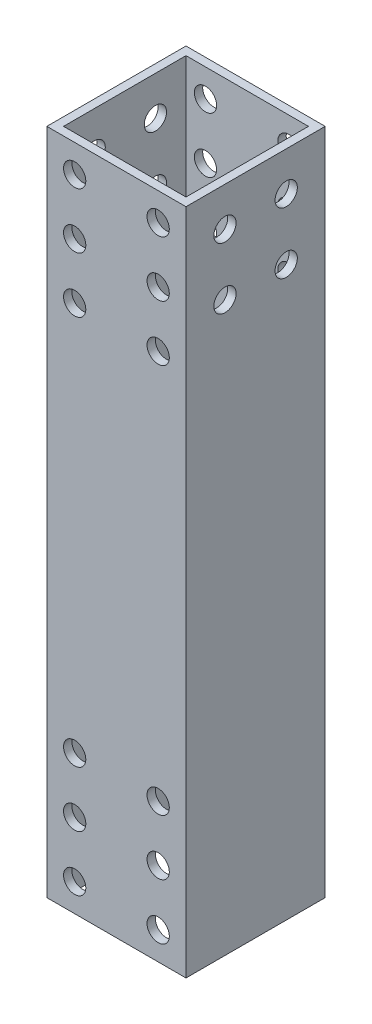
SolidWorks part; units mm, degrees
material "1060 Alloy"
ref_plane "Front Plane" through (0, 0, 0) normal (0, 0, 1) x (1, 0, 0)
ref_plane "Top Plane" through (0, 0, 0) normal (0, 1, 0) x (1, 0, 0)
ref_plane "Right Plane" through (0, 0, 0) normal (1, 0, 0) x (0, 0, -1)
sketch "Sketch1" plane through (0, 0, 0) normal (0, 1, 0) x (1, 0, 0)
  line L0 (0, 63.6278) -> (0, -69.3975) construction
  line L1 (-105.4586, 0) -> (105.4586, 0) construction
  line L2 (-11, 11) -> (-11, -11)
  line L3 (-12.5, 12.5) -> (12.5, 12.5)
  line L4 (-12.5, 12.5) -> (-12.5, -12.5)
  line L5 (-12.5, -12.5) -> (12.5, -12.5)
  line L6 (12.5, 12.5) -> (12.5, -12.5)
  line L7 (-11, -11) -> (11, -11)
  line L8 (11, 11) -> (11, -11)
  line L13 (-11, 11) -> (11, 11)
  point P5 (0, 0)
  dimension "D1" = 25
  dimension "D2" = 25
  dimension "D3" = 0
  dimension "D4" = 1.5
  dimension "D5" = 11
  dimension "D6" = 11
extrude "Boss-Extrude1" add sketch "Sketch1" along normal blind 60 and the other way blind 60
sketch "Sketch2" plane through (0, 0, -12.5) normal (0, 0, -1) x (-1, 0, 0)
  line L0 (0, 86.3155) -> (0, -83.2573) construction
  line L1 (-12.5, 60) -> (12.5, 60) construction
  circle A0 centre (7.5, 55) radius 2
  circle A1 centre (7.5, 45) radius 2
  circle A3 centre (-7.5, 55) radius 2
  circle A4 centre (-7.5, 45) radius 2
  circle A5 centre (7.5, 35) radius 2
  circle A6 centre (-7.5, 35) radius 2
  dimension "D1" = 7.5
  dimension "D5" = 10
  dimension "D2" = 7.5
  dimension "D3" = 7.5
  dimension "D4" = 7.5
  dimension "D6" = 10
  dimension "D7" = 5
  dimension "D8" = 10
  dimension "D9" = 7.5
  dimension "D10" = 5
  dimension "D11" = 10
  dimension "D12" = 7.5
extrude "Cut-Extrude1" cut sketch "Sketch2" against normal blind 25
mirror "Mirror1" about plane through (0, 0, 0) normal (0, 1, 0) of "Cut-Extrude1"
sketch "Sketch3" plane through (12.5, 0, 0) normal (1, 0, 0) x (0, 0, -1)
  line L0 (12.5, -60) -> (12.5, 60) construction
  line L1 (-12.5, 60) -> (12.5, 60) construction
  line L2 (-12.5, -60) -> (-12.5, 60) construction
  circle A0 centre (5.5, 53) radius 2
  circle A1 centre (5.5, 42) radius 2
  circle A2 centre (-5.5, 53) radius 2
  circle A3 centre (-5.5, 42) radius 2
  dimension "D1" = 7
  dimension "D2" = 7
  dimension "D3" = 7
  dimension "D4" = 7
  dimension "D5" = 11
  dimension "D6" = 11
  dimension "D7" = 7
  dimension "D8" = 7
extrude "Cut-Extrude2" cut sketch "Sketch3" against normal blind 25
